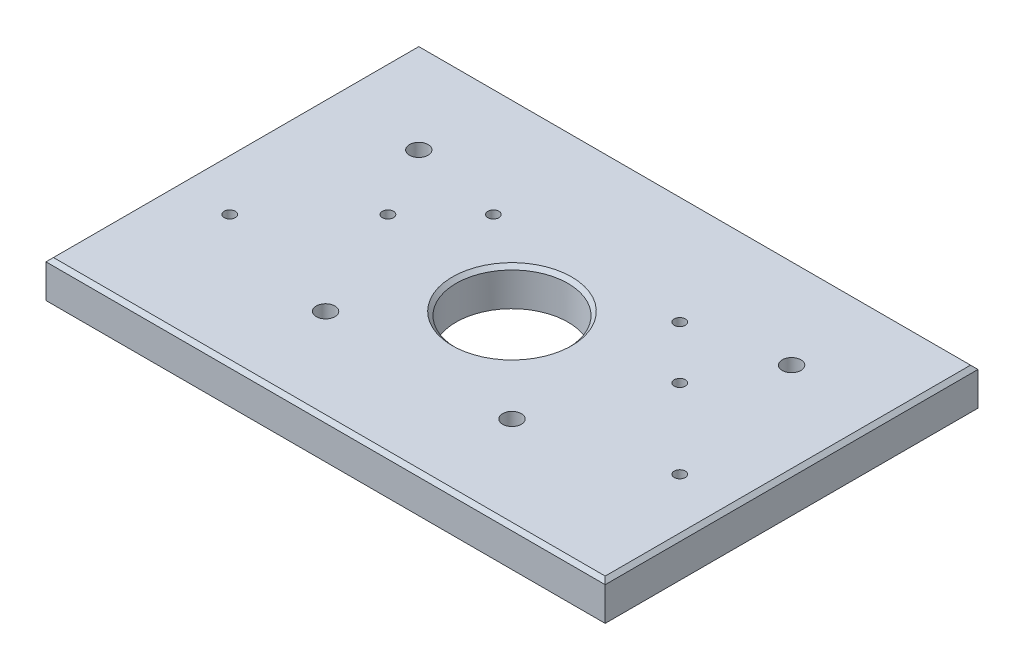
SolidWorks part; units mm, degrees
ref_plane "Front Plane" through (0, 0, 0) normal (0, 0, 1) x (1, 0, 0)
ref_plane "Top Plane" through (0, 0, 0) normal (0, 1, 0) x (1, 0, 0)
ref_plane "Right Plane" through (0, 0, 0) normal (1, 0, 0) x (0, 0, -1)
sketch "Sketch1" plane through (0, 0, 0) normal (0, 1, 0) x (1, 0, 0)
  line L1 (0, 0) -> (150, 0)
  line L2 (0, 0) -> (0, 100)
  line L3 (0, 100) -> (150, 100)
  line L4 (150, 0) -> (150, 100)
  dimension "D1" = 100
  dimension "D2" = 150
extrude "Boss-Extrude1" add sketch "Sketch1" along normal blind 10
sketch "Sketch2" plane through (0, 10, 0) normal (0, 1, 0) x (1, 0, 0)
  line L0 (0, 100) -> (0, 0) construction
  line L1 (150, 100) -> (0, 100) construction
  line L2 (50, 70) -> (0, 20) construction
  line L3 (35.8579, 55.8579) -> (14.6447, 34.6447) construction
  line L4 (75, 100) -> (75, 0) construction
  line L5 (0, 0) -> (150, 0) construction
  line L6 (100, 70) -> (150, 20) construction
  circle A0 centre (50, 70) radius 1.5
  circle A1 centre (35.8579, 55.8579) radius 1.5
  circle A2 centre (14.6447, 34.6447) radius 1.5
  circle A3 centre (75, 50) radius 15
  circle A4 centre (50, 25) radius 2.5
  circle A5 centre (25, 75) radius 2.5
  circle A6 centre (125, 75) radius 2.5
  circle A7 centre (100, 25) radius 2.5
  circle A8 centre (135.3553, 34.6447) radius 1.5
  circle A9 centre (114.1421, 55.8579) radius 1.5
  circle A10 centre (100, 70) radius 1.5
  point P14 (75, 71.317)
  point P19 (24.043, 71.3424)
  point P24 (0, 0)
  dimension "D1" = 3
  dimension "D7" = 30
  dimension "D9" = 25
  dimension "D11" = 5
  dimension "D2" = 50
  dimension "D3" = 30
  dimension "D4" = 45
  dimension "D5" = 20
  dimension "D6" = 30
  dimension "D10" = 25
  dimension "D12" = 25
  dimension "D13" = 25
extrude "Cut-Extrude1" cut sketch "Sketch2" against normal through all contours A3 | A10 | A6 | A9 | A8 | A7 | A4 | A2 | A1 | A0 | A5 region at (75, 10, -50)
chamfer "Chamfer1" distance 1 angle 45 5 edges at (75, 10, -35) (150, 10, -50) (75, 10, -100) (0, 10, -50) (75, 10, 0)
